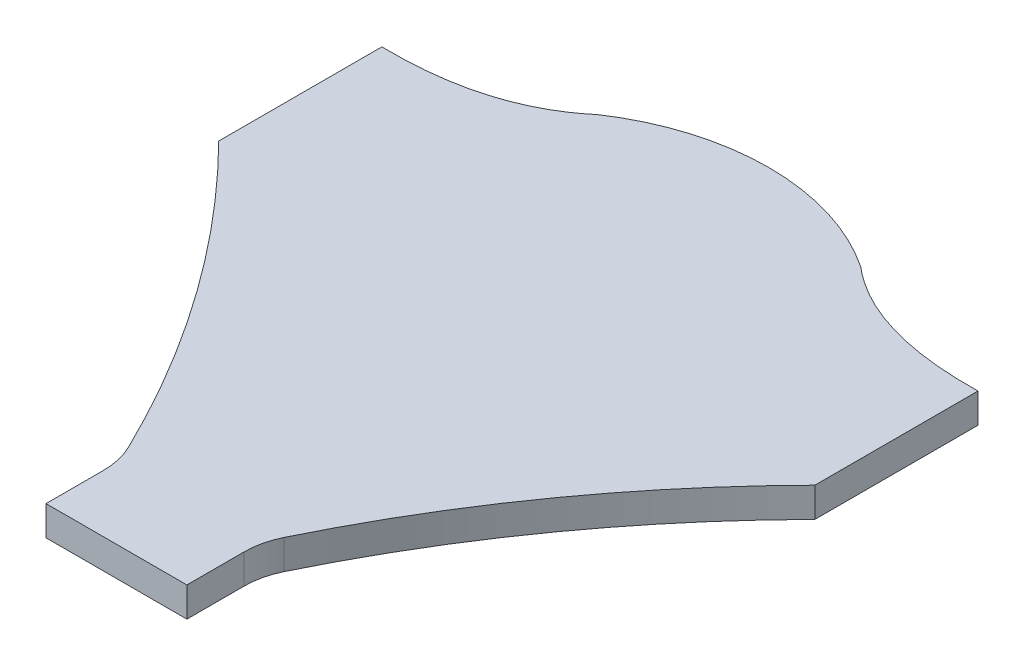
SolidWorks part; units mm, degrees
ref_plane "Front Plane" through (0, 0, 0) normal (0, 0, 1) x (1, 0, 0)
ref_plane "Top Plane" through (0, 0, 0) normal (0, 1, 0) x (1, 0, 0)
ref_plane "Right Plane" through (0, 0, 0) normal (1, 0, 0) x (0, 0, -1)
sketch "Sketch1" plane through (0, 0, 0) normal (0, 1, 0) x (1, 0, 0)
  line L0 (0, 0) -> (0, 25.4) construction
  line L1 (0, 25.4) -> (-67.3263, 25.4) construction
  line L2 (51.054, 0) -> (51.054, 25.4)
  line L3 (-51.054, 0) -> (-51.054, 25.4)
  line L4 (0, 0) -> (0, -2.54)
  line L5 (-51.054, 0) -> (-51.054, -2.54)
  line L6 (51.054, 0) -> (51.054, -2.54)
  line L7 (0, 0) -> (0, -2.54)
  line L8 (12.065, -71.12) -> (-12.065, -71.12)
  line L10 (-12.065, -58.42) -> (-12.065, -71.12)
  line L11 (12.065, -58.42) -> (12.065, -71.12)
  arc A0 (-34.5039, -21.473) -> (-30.5529, -26.7979) centre (0, 0) ccw
  arc A1 (25.874, 31.3392) -> (-25.874, 31.3392) centre (0, 0) ccw
  arc A2 (30.5529, -26.7979) -> (34.5039, -21.473) centre (0, 0) ccw
  spline S0 degree 2 poles (-51.054, -2.54) (-26.746, -27.0772) (-12.065, -58.42) knots 0 0 0 1 1 1
  spline S1 degree 2 poles (51.054, -2.54) (26.746, -27.0772) (12.065, -58.42) knots 0 0 0 1 1 1
  spline S2 degree 2 poles (-51.054, 25.4) (-32.8121, 25.0303) (-22.5628, 33.8013) knots 0 0 0 0.488429 0.488429 0.488429
  spline S3 degree 2 poles (51.054, 25.4) (32.8121, 25.0303) (22.5628, 33.8013) knots 0 0 0 0.488429 0.488429 0.488429
  point P19 (0, -71.12)
  dimension "D1" = 81.28
  dimension "D2" = 25.4
  dimension "D5" = 2.54
  dimension "D9" = 24.13
  dimension "D3" = 51.054
  dimension "D4" = 51.054
  dimension "D6" = 51.054
  dimension "D7" = 51.054
extrude "Boss-Extrude1" add sketch "Sketch1" along normal blind 5.08 contours L2 S3 A1 S2 L3 L5 S0 L10 L8 L11 S1 L6 region at (0, 0, 6.1616)
fillet "Fillet1" radius 12.7 1 edges at (-12.065, 2.54, 58.42) type face fillet first side face at (-41.3067, 2.54, 16.51) second side face at (-12.065, 2.54, 64.77)
fillet "Fillet2" radius 12.7 1 edges at (12.065, 2.54, 58.42)
